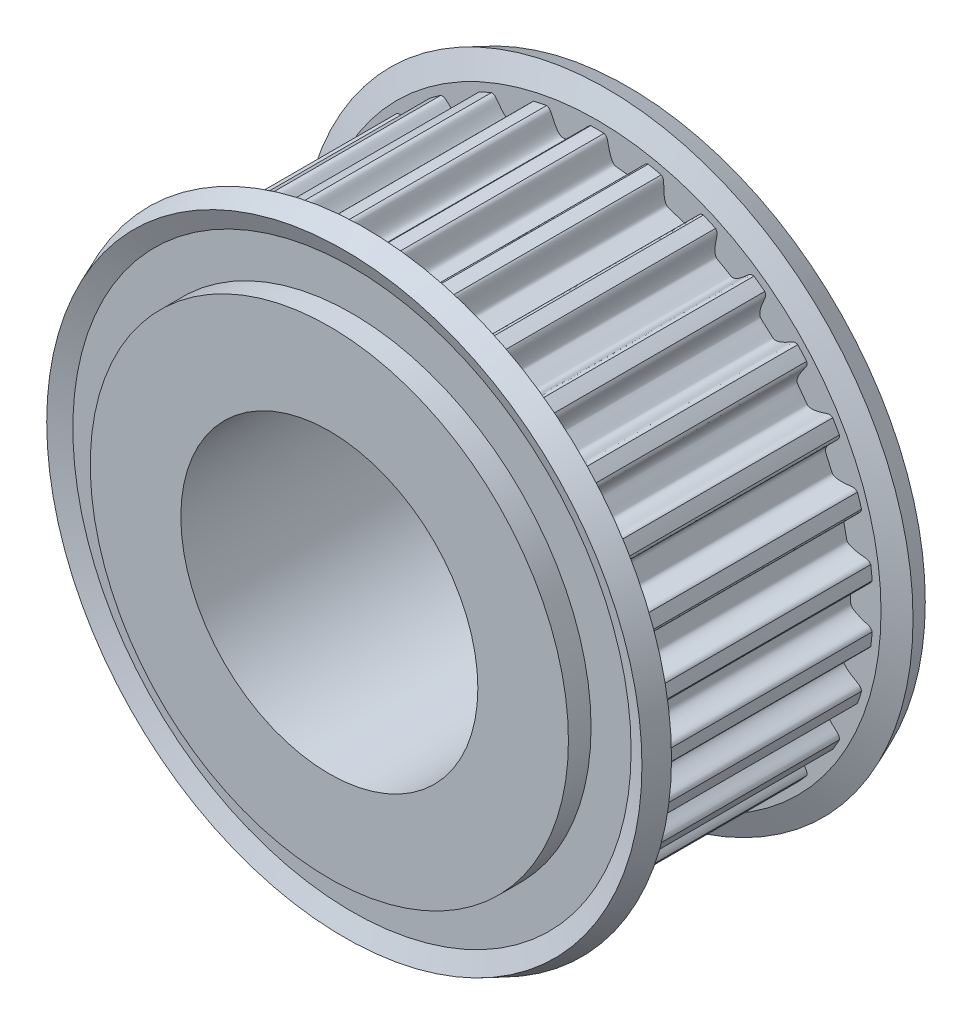
SolidWorks part; units mm, degrees
ref_plane "前视基准面" through (0, 0, 0) normal (0, 0, 1) x (1, 0, 0)
ref_plane "上视基准面" through (0, 0, 0) normal (0, 1, 0) x (1, 0, 0)
ref_plane "右视基准面" through (0, 0, 0) normal (1, 0, 0) x (0, 0, -1)
other "Configuration Table"
ref_axis "基准轴1" through (0, 0, 55) along (0, 0, -1)
sketch "SketchRevolveGearBelt01" plane through (0, 0, 0) normal (1, 0, 0) x (0, 0, -1)
  line L0 (0, 0) -> (1, 0) construction
  line L1 (5.274, 0) -> (5.274, 8.0493)
  line L2 (5.274, 8.0493) -> (4.512, 8.0493)
  line L3 (4.512, 8.0493) -> (4.512, 9.3977)
  line L4 (4.512, 9.3977) -> (4.7696, 10.0197)
  line L5 (4.7696, 10.0197) -> (4.0656, 10.3113)
  line L6 (4.0656, 10.3113) -> (3.75, 9.5493)
  line L7 (3.75, 9.5493) -> (3.75, 9.2805)
  line L8 (3.75, 9.2805) -> (-3.75, 9.2805)
  line L9 (-3.75, 9.2805) -> (-3.75, 9.5493)
  line L10 (-3.75, 9.5493) -> (-4.0656, 10.3113)
  line L11 (-4.0656, 10.3113) -> (-4.7696, 10.0197)
  line L12 (-4.7696, 10.0197) -> (-4.512, 9.3977)
  line L13 (-4.512, 9.3977) -> (-4.512, 8.0493)
  line L14 (-4.512, 8.0493) -> (-5.274, 8.0493)
  line L15 (-5.274, 8.0493) -> (-5.274, 0)
  line L16 (-5.274, 0) -> (5.274, 0)
  dimension "GearBeltFlange1OutsideLength" = 1.3484
  dimension "GearBeltFlange1X" = 0.2576
  dimension "GearBeltFlange1Y" = 0.622
  dimension "GearBeltFlangeThickness" = 0.762
  dimension "GearBeltFlangeInside" = 0.2688
  dimension "GearBeltOutsideDiameter" = 9.2805
  dimension "GearBeltFlange2X" = 0.2576
revolve "Gates_PowerGrip_GT_2mm, 6mm Belt Width" add sketch "SketchRevolveGearBelt01" angle 360 about L0
sketch "SketchToothGearBelt01" plane through (0, 0, 0) normal (0, 0, 1) x (1, 0, 0)
  arc A0 (9.2595, 0.8121) -> (9.2595, -0.8121) centre (0, 0) cw
  spline S0 degree 3 poles (9.2595, -0.8121) (9.2599, -0.7989) (9.2585, -0.7791) (9.2529, -0.7533) (9.2468, -0.7345) (9.2388, -0.7164) (9.2291, -0.6991) (9.2177, -0.6829) (9.2048, -0.6679) (9.1905, -0.6543) (9.1749, -0.6421) (9.1582, -0.6315) (9.1405, -0.6226) (9.0968, -0.6066) (9.0407, -0.5893) (8.974, -0.5675) (8.9232, -0.5498) (8.8755, -0.5322) (8.8309, -0.5145) (8.7894, -0.4969) (8.7509, -0.4793) (8.7155, -0.4616) (8.6831, -0.444) (8.6538, -0.4264) (8.6276, -0.4087) (8.6044, -0.3911) (8.5843, -0.3734) (8.5673, -0.3558) (8.5533, -0.3381) (8.5423, -0.3203) (8.5345, -0.3025) (8.5296, -0.2846) (8.5275, -0.2503) (8.5312, -0.2) (8.5317, -0.1333) (8.5327, -0.0666) (8.5328, 0) (8.5327, 0.0666) (8.5317, 0.1333) (8.5312, 0.2) (8.5275, 0.2503) (8.5296, 0.2846) (8.5345, 0.3025) (8.5423, 0.3203) (8.5533, 0.3381) (8.5673, 0.3558) (8.5843, 0.3734) (8.6044, 0.3911) (8.6276, 0.4087) (8.6538, 0.4264) (8.6831, 0.444) (8.7155, 0.4616) (8.7509, 0.4793) (8.7894, 0.4969) (8.8309, 0.5145) (8.8755, 0.5322) (8.9232, 0.5498) (8.974, 0.5675) (9.0407, 0.5893) (9.0968, 0.6066) (9.1405, 0.6226) (9.1582, 0.6315) (9.1749, 0.6421) (9.1905, 0.6543) (9.2048, 0.6679) (9.2177, 0.6829) (9.2291, 0.6991) (9.2388, 0.7164) (9.2468, 0.7345) (9.2529, 0.7533) (9.2585, 0.7791) (9.2599, 0.7989) (9.2595, 0.8121) knots 0 0 0 0 0.015924 0.023886 0.031848 0.03981 0.047771 0.055733 0.063695 0.071657 0.079619 0.087581 0.095543 0.103505 0.143783 0.166612 0.188267 0.208755 0.228086 0.24627 0.26332 0.279253 0.294087 0.307847 0.320562 0.332271 0.343022 0.352878 0.361922 0.370259 0.378023 0.385381 0.392526 0.419433 0.446289 0.473144 0.5 0.526856 0.553711 0.580567 0.607474 0.614619 0.621977 0.629741 0.638078 0.647122 0.656978 0.667729 0.679438 0.692153 0.705913 0.720747 0.73668 0.75373 0.771914 0.791245 0.811733 0.833388 0.856217 0.896495 0.904457 0.912419 0.920381 0.928343 0.936305 0.944267 0.952229 0.96019 0.968152 0.976114 0.984076 1 1 1 1
extrude "ToothExtrudeCutGearBelt01" cut sketch "SketchToothGearBelt01" against normal blind 3.75 and the other way blind 3.75
pattern_circular "Tooth Pattern, 30" count 30 every 12 about axis through (0, 0, 55) along (0, 0, -1) of "ToothExtrudeCutGearBelt01"
sketch "BoreRevolveSketch" plane through (0, 0, 0) normal (1, 0, 0) x (0, 0, -1)
  line L0 (0, 0) -> (1, 0) construction
  line L1 (-5.274, 0) -> (5.274, 0)
  line L2 (5.274, 0) -> (5.274, 5)
  line L3 (5.274, 5) -> (-5.274, 5)
  line L4 (-5.274, 5) -> (-5.274, 0)
  dimension "TaperSide1" = 5
  dimension "TaperSide2" = 5
revolve "BoreRevolveCut" cut sketch "BoreRevolveSketch" angle 360 about L0
sketch "AuxiliarySketchGearBelt01" plane through (0, 0, 0) normal (0, 0, 1) x (1, 0, 0)
  circle A0 centre (0, 0) radius 9.5493 construction
  dimension "PitchDiameter" = 19.0986
